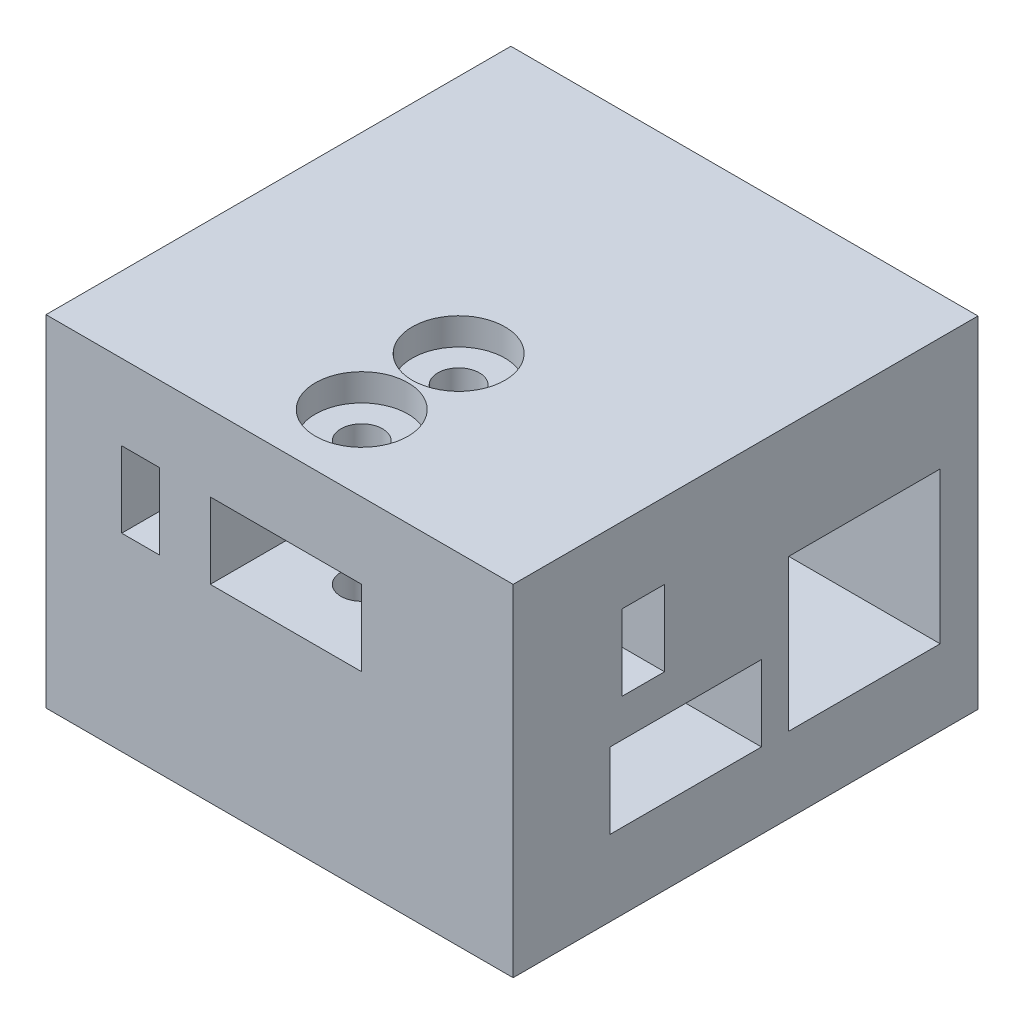
SolidWorks part; units mm, degrees
material "PET"
ref_plane "Front Plane" through (0, 0, 0) normal (0, 0, 1) x (1, 0, 0)
ref_plane "Top Plane" through (0, 0, 0) normal (0, 1, 0) x (1, 0, 0)
ref_plane "Right Plane" through (0, 0, 0) normal (1, 0, 0) x (0, 0, -1)
ref_plane "Bottom Idler Bottom Plane" through (0, 10, 0) normal (0, 1, 0) x (1, 0, 0)
ref_plane "Bottom Idler Top Plane" through (0, 20, 0) normal (0, 1, 0) x (1, 0, 0)
ref_plane "Top Idler Bottom Plane" through (0, 25, 0) normal (0, 1, 0) x (1, 0, 0)
ref_plane "Top Idler Top Plane" through (0, 35, 0) normal (0, 1, 0) x (1, 0, 0)
ref_plane "Top Of Part Plane" through (0, 45, 0) normal (0, 1, 0) x (1, 0, 0)
ref_plane "TopOfExtrusionPlane" through (0, 30, 0) normal (0, 1, 0) x (1, 0, 0)
ref_plane "Nut Trap Depth Plane" through (0, 4, 0) normal (0, 1, 0) x (1, 0, 0)
sketch "Idler Layout" plane through (0, 0, 0) normal (0, 1, 0) x (1, 0, 0)
  line L0 (0, 0) -> (0, 20)
  line L1 (0, 20) -> (20, 20)
  line L2 (20, 20) -> (20, 0)
  line L3 (20, 0) -> (0, 0)
  line L4 (0, 0) -> (0, -15)
  line L5 (0, -15) -> (20, -15)
  line L6 (20, -15) -> (20, 0)
  line L7 (0, 20) -> (-10, 20)
  line L8 (-10, 20) -> (-10, -15)
  line L9 (-10, -15) -> (0, -15)
  line L10 (-10, -15) -> (-10, -20)
  line L11 (-10, -20) -> (20, -20)
  line L12 (20, -20) -> (20, -15)
  line L13 (-10, -26.4) -> (-29.2, -26.4)
  line L14 (-10, -15) -> (-41.7, -15)
  line L15 (-31.7, -21.4) -> (-26.7, -21.4)
  line L16 (-31.7, -21.4) -> (-31.7, -31.4)
  line L17 (-31.7, -31.4) -> (-26.7, -31.4)
  line L18 (-26.7, -21.4) -> (-26.7, -31.4)
  line L19 (-31.7, -21.4) -> (-26.7, -31.4) construction
  line L20 (-31.7, -31.4) -> (-26.7, -21.4) construction
  line L21 (-41.7, -15) -> (-41.7, 20)
  line L22 (-41.7, 20) -> (-10, 20)
  line L23 (-41.7, -15) -> (-41.7, -36.4)
  line L24 (-41.7, -36.4) -> (20, -36.4)
  line L25 (20, -36.4) -> (20, -20)
  line L26 (-41.7, 20) -> (-41.7, 25)
  line L27 (-41.7, 25) -> (20, 25)
  line L28 (20, 25) -> (20, 20)
  arc A0 (-10, -20) -> (-16.4, -26.4) centre (-10, -26.4) ccw
  arc A1 (-19, -26.4) -> (-10, -17.4) centre (-10, -26.4) cw
  arc A2 (-20, -26.4) -> (-10, -16.4) centre (-10, -26.4) cw
  arc A3 (-10, -20) -> (-16.4, -13.6) centre (-10, -13.6) cw
  arc A4 (-19, -13.6) -> (-10, -22.6) centre (-10, -13.6) ccw
  arc A5 (-10, -23.6) -> (-20, -13.6) centre (-10, -13.6) cw
  dimension "D6" = 6.4
  dimension "D7" = 9
  dimension "D8" = 10
  dimension "D9" = 19.2
  dimension "D1" = 5
  dimension "D2" = 20
  dimension "D3" = 20
  dimension "D4" = 15
  dimension "D5" = 10
  dimension "D10" = 5
  dimension "D11" = 10
  dimension "D12" = 10
  dimension "D13" = 10
  dimension "D14" = 5
ref_plane "Left Side Plane" through (-41.7, 0, 0) normal (1, 0, 0) x (0, 0, -1)
ref_plane "ExtrusionMountingCounterbore Depth" through (-10, 0, 0) normal (-1, 0, 0) x (0, 0, 1)
ref_axis "Top Idler Axis" through (-10, 0, 26.4) along (0, 1, 0)
ref_axis "Bottom Idler Axis" through (-10, 0, 13.6) along (0, 1, 0)
sketch "MainBlockSketch" plane through (0, 0, 0) normal (0, 1, 0) x (1, 0, 0)
  line L0 (-41.7, -36.4) -> (20, -36.4) construction
  line L1 (-41.7, -15) -> (-41.7, -36.4) construction
  line L2 (20, -36.4) -> (20, -20) construction
  line L3 (20, -20) -> (20, -15) construction
  line L4 (20, -15) -> (20, 0) construction
  line L5 (20, 20) -> (20, 0) construction
  line L6 (20, 25) -> (20, 20) construction
  line L7 (-41.7, 25) -> (20, 25) construction
  line L8 (-41.7, 20) -> (-41.7, 25) construction
  line L9 (-41.7, -15) -> (-41.7, 20) construction
  line L10 (-41.7, -36.4) -> (20, -36.4)
  line L11 (-41.7, -15) -> (-41.7, -36.4)
  line L12 (20, -36.4) -> (20, -20)
  line L13 (20, -20) -> (20, -15)
  line L14 (20, -15) -> (20, 0)
  line L15 (20, 20) -> (20, 0)
  line L16 (20, 25) -> (20, 20)
  line L17 (-41.7, 25) -> (20, 25)
  line L18 (-41.7, 20) -> (-41.7, 25)
  line L19 (-41.7, -15) -> (-41.7, 20)
extrude "Main Block" add sketch "MainBlockSketch" along normal up to surface (45 mm away) up to plane "Top Of Part Plane"
sketch "Bottom Idler Cutout Sketch" plane through (0, 10, 0) normal (0, 1, 0) x (1, 0, 0)
  line L0 (-10, -23.6) -> (20, -23.6)
  line L1 (20, -36.4) -> (20, -20) construction
  line L2 (20, -23.6) -> (20, -3.6)
  line L3 (20, -15) -> (20, 0) construction
  line L4 (20, -3.6) -> (-10, -3.6)
  line L5 (-20, -13.6) -> (-20, 25)
  line L6 (-41.7, 25) -> (20, 25) construction
  line L7 (-20, 25) -> (-15, 25)
  line L9 (-15, 25) -> (-15, -4.9397)
  arc A0 (-20, -13.6) -> (-10, -23.6) centre (-10, -13.6) ccw
  arc A1 (-10, -3.6) -> (-15, -4.9397) centre (-10, -13.6) ccw
  dimension "D1" = 5
extrude "Bottom Idler Cutout" cut sketch "Bottom Idler Cutout Sketch" along normal up to surface (10 mm away) up to plane "Bottom Idler Top Plane"
sketch "Top Idler Cutout Sketch" plane through (0, 25, 0) normal (0, 1, 0) x (1, 0, 0)
  line L0 (-20, -26.4) -> (-20, -36.4)
  line L1 (-41.7, -36.4) -> (20, -36.4) construction
  line L2 (-10, -16.4) -> (20, -16.4)
  line L3 (20, -20) -> (20, -15) construction
  line L4 (20, -16.4) -> (20, -22)
  line L7 (0, -26.4) -> (0, -36.4)
  line L9 (20, -22) -> (-1.02, -22)
  line L10 (-20, -36.4) -> (0, -36.4)
  arc A2 (-10, -16.4) -> (-20, -26.4) centre (-10, -26.4) ccw
  arc A3 (0, -26.4) -> (-1.02, -22) centre (-10, -26.4) ccw
  dimension "D2" = 2
extrude "Top Idler Cutout" cut sketch "Top Idler Cutout Sketch" along normal up to surface (10 mm away) up to plane "Top Idler Top Plane"
sketch "Belt Passthrough Sketch" plane through (0, 25, 0) normal (0, 1, 0) x (1, 0, 0)
  line L1 (-41.7, -36.4) -> (20, -36.4) construction
  line L2 (-31.7, -36.4) -> (-26.7, -36.4)
  line L5 (-41.7, 25) -> (20, 25) construction
  line L6 (-26.7, 25) -> (-31.7, 25)
  line L8 (-31.7, 25) -> (-31.7, -36.4)
  line L9 (-26.7, 25) -> (-26.7, -36.4)
  line L10 (-31.7, -21.4) -> (-31.7, -31.4) construction
  line L11 (-26.7, -21.4) -> (-26.7, -31.4) construction
extrude "Belt Passthrough" cut sketch "Belt Passthrough Sketch" along normal up to surface (10 mm away) up to plane "Top Idler Top Plane"
sketch "2020VSlotCutoutSketch" plane through (0, 10, 0) normal (0, 1, 0) x (1, 0, 0)
  line L0 (20, 0) -> (0, 0) construction
  line L1 (20, 20) -> (20, 0) construction
  line L2 (0, 20) -> (20, 20) construction
  line L3 (0, 0) -> (0, 20) construction
  line L4 (20, 0) -> (0, 0)
  line L5 (20, 20) -> (20, 0)
  line L6 (0, 20) -> (20, 20)
  line L7 (0, 0) -> (0, 20)
extrude "ExtrusionMountingSlot" cut sketch "2020VSlotCutoutSketch" along normal up to surface (20 mm away) up to plane "TopOfExtrusionPlane"
hole_wizard "CBORE for M5 Hex Head Bolt1" positions "Sketch6" profile "Sketch7" counterbore size "M5" standard "ANSI Metric" end condition through all
sketch "Sketch6" plane through (0, 45, 0) normal (0, 1, 0) x (1, 0, 0)
  point P0 (-10, -26.4)
  point P3 (-10, -13.6)
sketch "Sketch7" plane through (-10, 45, 26.4) normal (1, 0, 0) x (0, 0, 1)
  line L0 (0, 0) -> (0, 45)
  line L1 (0, 45) -> (2.75, 45)
  line L3 (2.75, 45) -> (2.75, 3.58)
  line L4 (2.75, 3.58) -> (6.12, 3.58)
  line L5 (6.12, 3.58) -> (6.12, 0)
  line L7 (6.12, 0) -> (0, 0)
  line L11 (0, -6.35) -> (0, 107.95) construction
  dimension "Thru Hole Dia." = 5.5
  dimension "Thru Hole Depth" = 45
  dimension "C'Bore Dia." = 12.24
  dimension "C'Bore Depth" = 3.58
sketch "Nut Trap Sketch" plane through (0, 0, 0) normal (0, 1, 0) x (1, 0, 0)
  line L5 (-7.6329, -9.5) -> (-12.3671, -9.5)
  line L6 (-12.3671, -9.5) -> (-14.7343, -13.6)
  line L7 (-14.7343, -13.6) -> (-12.3671, -17.7)
  line L8 (-12.3671, -17.7) -> (-7.6329, -17.7)
  line L9 (-7.6329, -17.7) -> (-5.2657, -13.6)
  line L10 (-5.2657, -13.6) -> (-7.6329, -9.5)
  line L11 (-7.6329, -22.3) -> (-12.3671, -22.3)
  line L12 (-12.3671, -22.3) -> (-14.7343, -26.4)
  line L13 (-14.7343, -26.4) -> (-12.3671, -30.5)
  line L14 (-12.3671, -30.5) -> (-7.6329, -30.5)
  line L15 (-7.6329, -30.5) -> (-5.2657, -26.4)
  line L16 (-5.2657, -26.4) -> (-7.6329, -22.3)
  circle A0 centre (-10, -13.6) radius 4.1 construction
  circle A1 centre (-10, -26.4) radius 4.1 construction
  dimension "D5" = 8.2
extrude "NutTraps" cut sketch "Nut Trap Sketch" along normal up to surface (4 mm away) up to plane "Nut Trap Depth Plane"
sketch "ExtrusionMountingCounterBoreSketch" plane through (-41.7, 0, 0) normal (1, 0, 0) x (0, 0, -1)
  line L0 (45.3943, 10) -> (-45.3943, 10) construction
  line L3 (10, 10) -> (10, 20) construction
  circle A0 centre (10, 20) radius 4.5
  point P1 (10, 20.9477)
  point P5 (0, 0)
  dimension "D3" = 9
  dimension "D1" = 10
  dimension "D2" = 10
extrude "ExtrusionMountingCounterbore" cut sketch "ExtrusionMountingCounterBoreSketch" along normal up to surface (31.7 mm away) up to plane "ExtrusionMountingCounterbore Depth"
sketch "ExtrusionMountingHoleSketch" plane through (-10, 0, 0) normal (-1, 0, 0) x (0, 0, 1)
  circle A0 centre (-10, 20) radius 2.65
  dimension "D1" = 5.3
extrude "extrusionMountingHole" cut sketch "ExtrusionMountingHoleSketch" against normal through all
